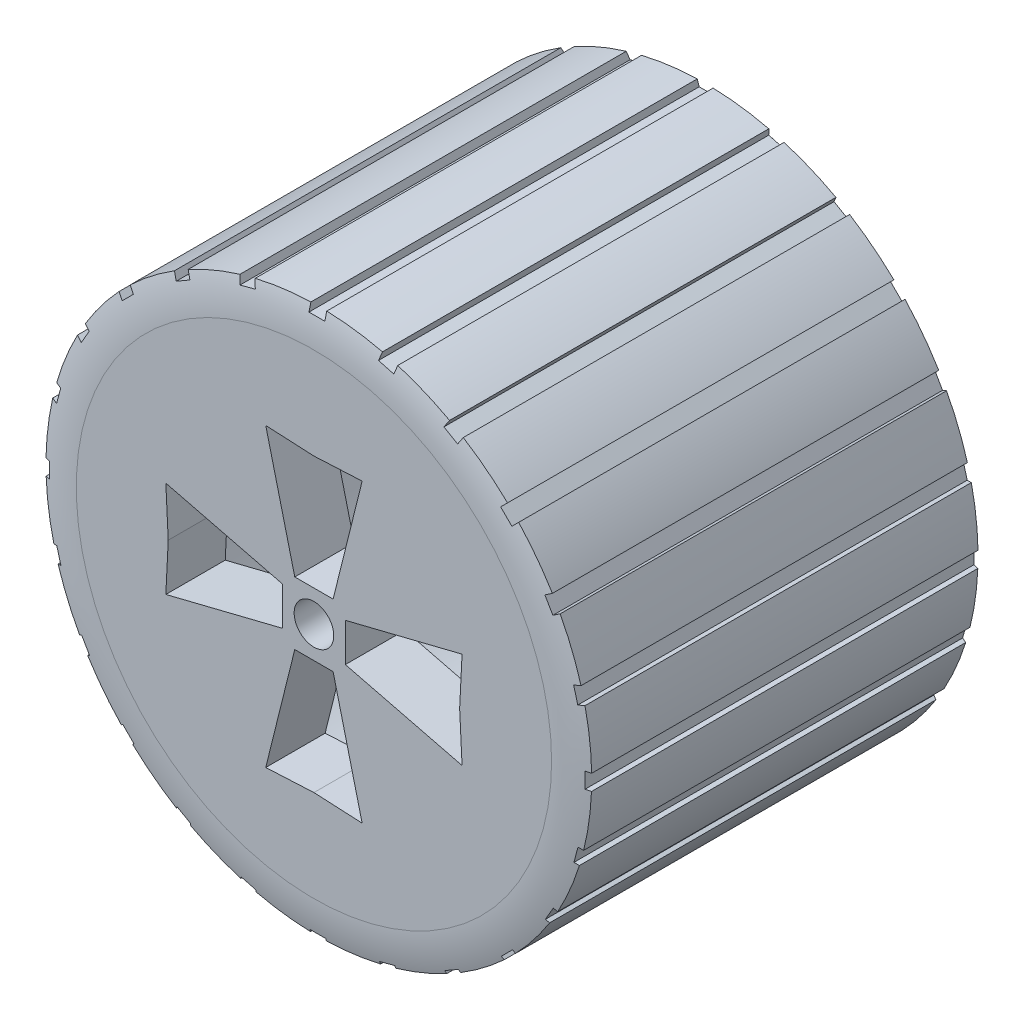
SolidWorks part; units mm, degrees
ref_plane "Front Plane" through (0, 0, 0) normal (0, 0, 1) x (1, 0, 0)
ref_plane "Top Plane" through (0, 0, 0) normal (0, 1, 0) x (1, 0, 0)
ref_plane "Right Plane" through (0, 0, 0) normal (1, 0, 0) x (0, 0, -1)
sketch "Sketch2" plane through (0, 0, 0) normal (1, 0, 0) x (0, 0, -1)
  line L0 (-5, 4) -> (-5, 6)
  line L1 (-5, 6) -> (-4.2527, 6)
  line L2 (-4.2527, 6) -> (-3.5, 5.2473)
  line L3 (-3.5, 5.2473) -> (3.5, 5.2473)
  line L4 (-5, 4) -> (5, 4)
  line L5 (0, 0) -> (0, 8.4877) construction
  line L6 (-12.9973, 0) -> (13.1187, 0) construction
  line L7 (4.2527, 6) -> (3.5, 5.2473)
  line L8 (5, 6) -> (4.2527, 6)
  line L9 (5, 4) -> (5, 6)
  line L10 (-5, 4) -> (-5, 0)
  line L11 (-5, 0) -> (5, 0)
  line L12 (5, 0) -> (5, 4)
  line L13 (-4.8767, 6.8889) -> (4.8767, 6.8889)
  arc A0 (-5, 6) -> (-4.8767, 6.8889) centre (-1.7351, 6) cw
  arc A1 (5, 6) -> (4.8767, 6.8889) centre (1.7351, 6) ccw
  point P13 (0, 5.2473)
  point P15 (0, 4)
  point P22 (0, 6.8889)
  dimension "D1" = 4
  dimension "D2" = 3.5
  dimension "D3" = 5
  dimension "D4" = 2
  dimension "D5" = 0.7527
revolve "Revolve1" add sketch "Sketch2" angle 360 about L6 region at (0, 4.738, 0) region at (0, 2, 0) other way angle 360
sketch "Sketch3" plane through (0, 0, 0) normal (0, 0, 1) x (1, 0, 0)
  circle A0 centre (0, 0) radius 0.5
  dimension "D1" = 1
extrude "Cut-Extrude1" cut sketch "Sketch3" against normal through all both and the other way through all
sketch "Sketch4" plane through (0, 0, 0) normal (0, 0, 1) x (1, 0, 0)
  circle A0 centre (0, 0) radius 5
  dimension "D1" = 10
extrude "Cut-Extrude4" cut sketch "Sketch4" against normal through all and the other way blind 3.5 contours A0
sketch "Sketch6" plane through (0, 0, 5) normal (0, 0, 1) x (1, 0, 0)
  line L3 (0, 0) -> (0, 4.3788) construction
  line L27 (-0.484, 0.7934) -> (-1.217, 3.7392)
  line L28 (-1.217, 3.7392) -> (0, 3.6785)
  line L29 (-0.484, 0.7934) -> (0.484, 0.7934)
  line L30 (0.484, 0.7934) -> (1.217, 3.7392)
  line L31 (1.217, 3.7392) -> (0, 3.6785)
  line L32 (0.7934, 0.484) -> (0.7934, -0.484)
  line L33 (0.7934, -0.484) -> (3.7392, -1.217)
  line L34 (3.7392, -1.217) -> (3.6785, 0)
  line L35 (3.7392, 1.217) -> (3.6785, 0)
  line L36 (0.7934, 0.484) -> (3.7392, 1.217)
  line L37 (0.484, -0.7934) -> (-0.484, -0.7934)
  line L38 (-0.484, -0.7934) -> (-1.217, -3.7392)
  line L39 (-1.217, -3.7392) -> (0, -3.6785)
  line L40 (1.217, -3.7392) -> (0, -3.6785)
  line L41 (0.484, -0.7934) -> (1.217, -3.7392)
  line L42 (-0.7934, -0.484) -> (-0.7934, 0.484)
  line L43 (-0.7934, 0.484) -> (-3.7392, 1.217)
  line L44 (-3.7392, 1.217) -> (-3.6785, 0)
  line L45 (-3.7392, -1.217) -> (-3.6785, 0)
  line L46 (-0.7934, -0.484) -> (-3.7392, -1.217)
  point P8 (0, 0.7934)
  point P24 (0, -1.1729)
  point P28 (0, 0)
  dimension "D1" = 4
extrude "Cut-Extrude8" cut sketch "Sketch6" against normal blind 1.5
revolve "Revolve2" add sketch "Sketch2<3>" angle 360 about L6 region at (0, 6.1213, 0)
sketch "Sketch2<3>" plane through (0, 0, 0) normal (1, 0, 0) x (0, 0, -1) same geometry as "Sketch2"
sketch "Sketch7" plane through (0, 0, 0) normal (0, 0, 1) x (1, 0, 0)
  line L0 (1.6594, 6.8953) -> (1.9423, 6.4054) construction
  line L1 (-0.2, 7.0889) -> (0.2, 7.0889)
  line L2 (-0.2, 7.0889) -> (-0.2, 6.6889)
  line L3 (-0.2, 6.6889) -> (0.2, 6.6889)
  line L4 (0.2, 7.0889) -> (0.2, 6.6889)
  line L5 (-0.2, 7.0889) -> (0.2, 6.6889) construction
  line L6 (-0.2, 6.6889) -> (0.2, 7.0889) construction
  line L7 (1.5559, 6.5089) -> (2.0458, 6.7918) construction
  line L8 (1.6594, 6.8953) -> (2.0458, 6.7918)
  line L9 (1.6594, 6.8953) -> (1.5559, 6.5089)
  line L10 (2.0458, 6.7918) -> (1.9423, 6.4054)
  line L11 (1.5559, 6.5089) -> (1.9423, 6.4054)
  line L12 (3.4054, 6.2271) -> (3.5518, 5.6806) construction
  line L13 (3.2054, 5.8806) -> (3.7518, 6.0271) construction
  line L14 (3.4054, 6.2271) -> (3.7518, 6.0271)
  line L15 (3.4054, 6.2271) -> (3.2054, 5.8806)
  line L16 (3.7518, 6.0271) -> (3.5518, 5.6806)
  line L17 (3.2054, 5.8806) -> (3.5518, 5.6806)
  line L18 (4.9189, 5.1297) -> (4.9189, 4.564) construction
  line L19 (4.636, 4.8468) -> (5.2017, 4.8468) construction
  line L20 (4.9189, 5.1297) -> (5.2017, 4.8468)
  line L21 (4.9189, 5.1297) -> (4.636, 4.8468)
  line L22 (5.2017, 4.8468) -> (4.9189, 4.564)
  line L23 (4.636, 4.8468) -> (4.9189, 4.564)
  line L24 (6.0968, 3.678) -> (5.9504, 3.1316) construction
  line L25 (5.7504, 3.478) -> (6.2968, 3.3316) construction
  line L26 (6.0968, 3.678) -> (6.2968, 3.3316)
  line L27 (6.0968, 3.678) -> (5.7504, 3.478)
  line L28 (6.2968, 3.3316) -> (5.9504, 3.1316)
  line L29 (5.7504, 3.478) -> (5.9504, 3.1316)
  line L30 (6.8588, 1.9709) -> (6.576, 1.481) construction
  line L31 (6.4725, 1.8673) -> (6.9624, 1.5845) construction
  line L32 (6.8588, 1.9709) -> (6.9624, 1.5845)
  line L33 (6.8588, 1.9709) -> (6.4725, 1.8673)
  line L34 (6.9624, 1.5845) -> (6.576, 1.481)
  line L35 (6.4725, 1.8673) -> (6.576, 1.481)
  line L36 (7.1531, 0.1247) -> (6.7531, -0.2753) construction
  line L37 (6.7531, 0.1247) -> (7.1531, -0.2753) construction
  line L38 (7.1531, 0.1247) -> (7.1531, -0.2753)
  line L39 (7.1531, 0.1247) -> (6.7531, 0.1247)
  line L40 (7.1531, -0.2753) -> (6.7531, -0.2753)
  line L41 (6.7531, 0.1247) -> (6.7531, -0.2753)
  line L42 (6.9595, -1.7347) -> (6.4696, -2.0176) construction
  line L43 (6.5731, -1.6312) -> (6.8559, -2.1211) construction
  line L44 (6.9595, -1.7347) -> (6.8559, -2.1211)
  line L45 (6.9595, -1.7347) -> (6.5731, -1.6312)
  line L46 (6.8559, -2.1211) -> (6.4696, -2.0176)
  line L47 (6.5731, -1.6312) -> (6.4696, -2.0176)
  line L48 (6.2912, -3.4807) -> (5.7448, -3.6271) construction
  line L49 (5.9448, -3.2807) -> (6.0912, -3.8271) construction
  line L50 (6.2912, -3.4807) -> (6.0912, -3.8271)
  line L51 (6.2912, -3.4807) -> (5.9448, -3.2807)
  line L52 (6.0912, -3.8271) -> (5.7448, -3.6271)
  line L53 (5.9448, -3.2807) -> (5.7448, -3.6271)
  line L54 (5.1938, -4.9942) -> (4.6281, -4.9942) construction
  line L55 (4.911, -4.7113) -> (4.911, -5.277) construction
  line L56 (5.1938, -4.9942) -> (4.911, -5.277)
  line L57 (5.1938, -4.9942) -> (4.911, -4.7113)
  line L58 (4.911, -5.277) -> (4.6281, -4.9942)
  line L59 (4.911, -4.7113) -> (4.6281, -4.9942)
  line L60 (3.7421, -6.1721) -> (3.1957, -6.0257) construction
  line L61 (3.5421, -5.8257) -> (3.3957, -6.3721) construction
  line L62 (3.7421, -6.1721) -> (3.3957, -6.3721)
  line L63 (3.7421, -6.1721) -> (3.5421, -5.8257)
  line L64 (3.3957, -6.3721) -> (3.1957, -6.0257)
  line L65 (3.5421, -5.8257) -> (3.1957, -6.0257)
  line L66 (2.035, -6.9341) -> (1.5451, -6.6513) construction
  line L67 (1.9315, -6.5478) -> (1.6486, -7.0377) construction
  line L68 (2.035, -6.9341) -> (1.6486, -7.0377)
  line L69 (2.035, -6.9341) -> (1.9315, -6.5478)
  line L70 (1.6486, -7.0377) -> (1.5451, -6.6513)
  line L71 (1.9315, -6.5478) -> (1.5451, -6.6513)
  line L72 (0.1888, -7.2284) -> (-0.2112, -6.8284) construction
  line L73 (0.1888, -6.8284) -> (-0.2112, -7.2284) construction
  line L74 (0.1888, -7.2284) -> (-0.2112, -7.2284)
  line L75 (0.1888, -7.2284) -> (0.1888, -6.8284)
  line L76 (-0.2112, -7.2284) -> (-0.2112, -6.8284)
  line L77 (0.1888, -6.8284) -> (-0.2112, -6.8284)
  line L78 (-1.6706, -7.0348) -> (-1.9534, -6.5449) construction
  line L79 (-1.5671, -6.6484) -> (-2.057, -6.9312) construction
  line L80 (-1.6706, -7.0348) -> (-2.057, -6.9312)
  line L81 (-1.6706, -7.0348) -> (-1.5671, -6.6484)
  line L82 (-2.057, -6.9312) -> (-1.9534, -6.5449)
  line L83 (-1.5671, -6.6484) -> (-1.9534, -6.5449)
  line L84 (-3.4165, -6.3665) -> (-3.563, -5.8201) construction
  line L85 (-3.2165, -6.0201) -> (-3.763, -6.1665) construction
  line L86 (-3.4165, -6.3665) -> (-3.763, -6.1665)
  line L87 (-3.4165, -6.3665) -> (-3.2165, -6.0201)
  line L88 (-3.763, -6.1665) -> (-3.563, -5.8201)
  line L89 (-3.2165, -6.0201) -> (-3.563, -5.8201)
  line L90 (-4.93, -5.2691) -> (-4.93, -4.7034) construction
  line L91 (-4.6472, -4.9863) -> (-5.2129, -4.9863) construction
  line L92 (-4.93, -5.2691) -> (-5.2129, -4.9863)
  line L93 (-4.93, -5.2691) -> (-4.6472, -4.9863)
  line L94 (-5.2129, -4.9863) -> (-4.93, -4.7034)
  line L95 (-4.6472, -4.9863) -> (-4.93, -4.7034)
  line L96 (-6.108, -3.8174) -> (-5.9615, -3.271) construction
  line L97 (-5.7615, -3.6174) -> (-6.308, -3.471) construction
  line L98 (-6.108, -3.8174) -> (-6.308, -3.471)
  line L99 (-6.108, -3.8174) -> (-5.7615, -3.6174)
  line L100 (-6.308, -3.471) -> (-5.9615, -3.271)
  line L101 (-5.7615, -3.6174) -> (-5.9615, -3.271)
  line L102 (-6.87, -2.1103) -> (-6.5872, -1.6204) construction
  line L103 (-6.4836, -2.0068) -> (-6.9735, -1.7239) construction
  line L104 (-6.87, -2.1103) -> (-6.9735, -1.7239)
  line L105 (-6.87, -2.1103) -> (-6.4836, -2.0068)
  line L106 (-6.9735, -1.7239) -> (-6.5872, -1.6204)
  line L107 (-6.4836, -2.0068) -> (-6.5872, -1.6204)
  line L108 (-7.1642, -0.2641) -> (-6.7642, 0.1359) construction
  line L109 (-6.7642, -0.2641) -> (-7.1642, 0.1359) construction
  line L110 (-7.1642, -0.2641) -> (-7.1642, 0.1359)
  line L111 (-7.1642, -0.2641) -> (-6.7642, -0.2641)
  line L112 (-7.1642, 0.1359) -> (-6.7642, 0.1359)
  line L113 (-6.7642, -0.2641) -> (-6.7642, 0.1359)
  line L114 (-6.9706, 1.5953) -> (-6.4807, 1.8781) construction
  line L115 (-6.5843, 1.4918) -> (-6.8671, 1.9816) construction
  line L116 (-6.9706, 1.5953) -> (-6.8671, 1.9816)
  line L117 (-6.9706, 1.5953) -> (-6.5843, 1.4918)
  line L118 (-6.8671, 1.9816) -> (-6.4807, 1.8781)
  line L119 (-6.5843, 1.4918) -> (-6.4807, 1.8781)
  line L120 (-6.3024, 3.3412) -> (-5.756, 3.4876) construction
  line L121 (-5.956, 3.1412) -> (-6.1024, 3.6876) construction
  line L122 (-6.3024, 3.3412) -> (-6.1024, 3.6876)
  line L123 (-6.3024, 3.3412) -> (-5.956, 3.1412)
  line L124 (-6.1024, 3.6876) -> (-5.756, 3.4876)
  line L125 (-5.956, 3.1412) -> (-5.756, 3.4876)
  line L126 (-5.205, 4.8547) -> (-4.6393, 4.8547) construction
  line L127 (-4.9221, 4.5719) -> (-4.9221, 5.1376) construction
  line L128 (-5.205, 4.8547) -> (-4.9221, 5.1376)
  line L129 (-5.205, 4.8547) -> (-4.9221, 4.5719)
  line L130 (-4.9221, 5.1376) -> (-4.6393, 4.8547)
  line L131 (-4.9221, 4.5719) -> (-4.6393, 4.8547)
  line L132 (-3.7533, 6.0326) -> (-3.2069, 5.8862) construction
  line L133 (-3.5533, 5.6862) -> (-3.4069, 6.2326) construction
  line L134 (-3.7533, 6.0326) -> (-3.4069, 6.2326)
  line L135 (-3.7533, 6.0326) -> (-3.5533, 5.6862)
  line L136 (-3.4069, 6.2326) -> (-3.2069, 5.8862)
  line L137 (-3.5533, 5.6862) -> (-3.2069, 5.8862)
  line L138 (-2.0462, 6.7947) -> (-1.5563, 6.5118) construction
  line L139 (-1.9426, 6.4083) -> (-1.6598, 6.8982) construction
  line L140 (-2.0462, 6.7947) -> (-1.6598, 6.8982)
  line L141 (-2.0462, 6.7947) -> (-1.9426, 6.4083)
  line L142 (-1.6598, 6.8982) -> (-1.5563, 6.5118)
  line L143 (-1.9426, 6.4083) -> (-1.5563, 6.5118)
  circle A0 centre (0, 0) radius 6.8889 construction
  point P0 (0, 6.8889)
  point P9 (1.8008, 6.6504)
  point P14 (3.4786, 5.9538)
  point P19 (4.9189, 4.8468)
  point P24 (6.0236, 3.4048)
  point P29 (6.7174, 1.7259)
  point P34 (6.9531, -0.0753)
  point P39 (6.7145, -1.8762)
  point P44 (6.018, -3.5539)
  point P49 (4.911, -4.9942)
  point P54 (3.4689, -6.0989)
  point P59 (1.7901, -6.7927)
  point P64 (-0.0112, -7.0284)
  point P69 (-1.812, -6.7898)
  point P74 (-3.4898, -6.0933)
  point P79 (-4.93, -4.9863)
  point P84 (-6.0348, -3.5442)
  point P89 (-6.7286, -1.8654)
  point P94 (-6.9642, -0.0641)
  point P99 (-6.7257, 1.7367)
  point P104 (-6.0292, 3.4144)
  point P109 (-4.9221, 4.8547)
  point P114 (-3.4801, 5.9594)
  point P119 (-1.8012, 6.6533)
  point P124 (-0.0056, -0.0697)
  dimension "D2" = 0.4
  dimension "D3" = 0.4
  dimension "D1" = 24
extrude "Cut-Extrude9" cut sketch "Sketch7" against normal through all both and the other way through all
